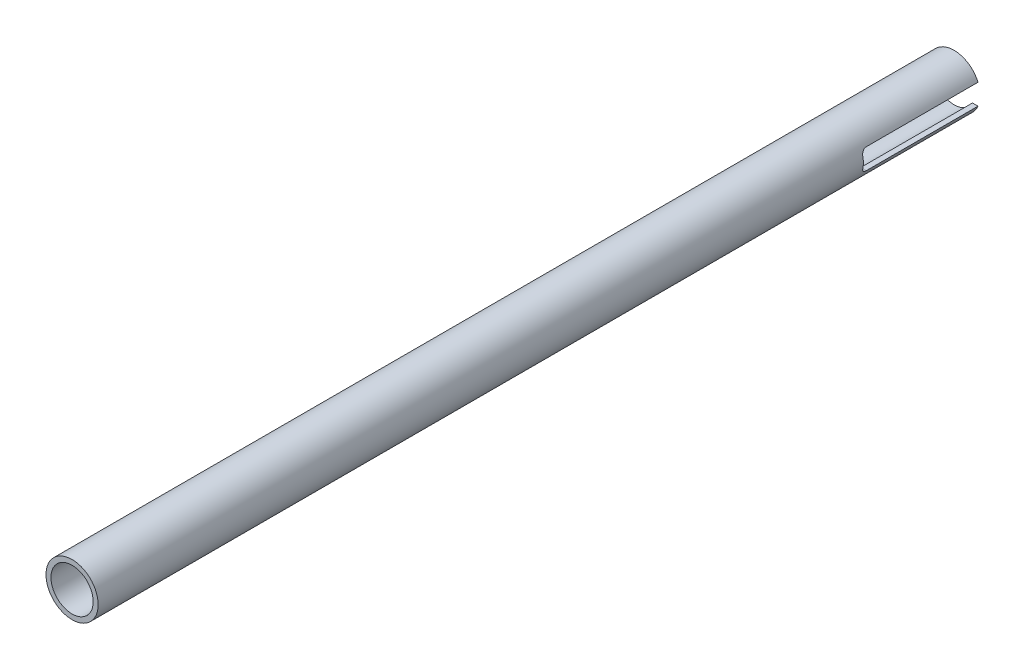
SolidWorks part; units mm, degrees
material "AISI 4130 Steel, annealed at 865C"
ref_plane "Front Plane" through (0, 0, 0) normal (0, 0, 1) x (1, 0, 0)
ref_plane "Top Plane" through (0, 0, 0) normal (0, 1, 0) x (1, 0, 0)
ref_plane "Right Plane" through (0, 0, 0) normal (1, 0, 0) x (0, 0, -1)
sketch "Sketch1" plane through (0, 0, 0) normal (0, 0, 1) x (1, 0, 0)
  circle A0 centre (0, 0) radius 6.477
  circle A1 centre (0, 0) radius 8.001
  dimension "D1" = 12.954
  dimension "D2" = 16.002
extrude "Boss-Extrude1" add sketch "Sketch1" along normal blind 270.51
sketch "Sketch2" plane through (0, 0, 0) normal (1, 0, 0) x (0, 0, -1)
  line L0 (0, 3.175) -> (-34.29, 3.175)
  line L1 (0, 8.8011) -> (0, -8.8011) construction
  line L2 (-34.29, -3.175) -> (0, -3.175)
  line L3 (-35.814, 1.651) -> (-35.814, -1.651)
  line L4 (0, -8.001) -> (0, 8.001) construction
  arc A0 (-35.814, 1.651) -> (-34.29, 3.175) centre (-34.29, 1.651) cw
  arc A1 (-34.29, -3.175) -> (-35.814, -1.651) centre (-34.29, -1.651) cw
  dimension "D5" = 34.29
  dimension "D6" = 35.814
  dimension "D1" = 35.814
  dimension "D2" = 34.29
  dimension "D3" = 6.35
  dimension "D4" = 3.175
extrude "Cut-Extrude1" cut sketch "Sketch2" against normal through all both and the other way through all
